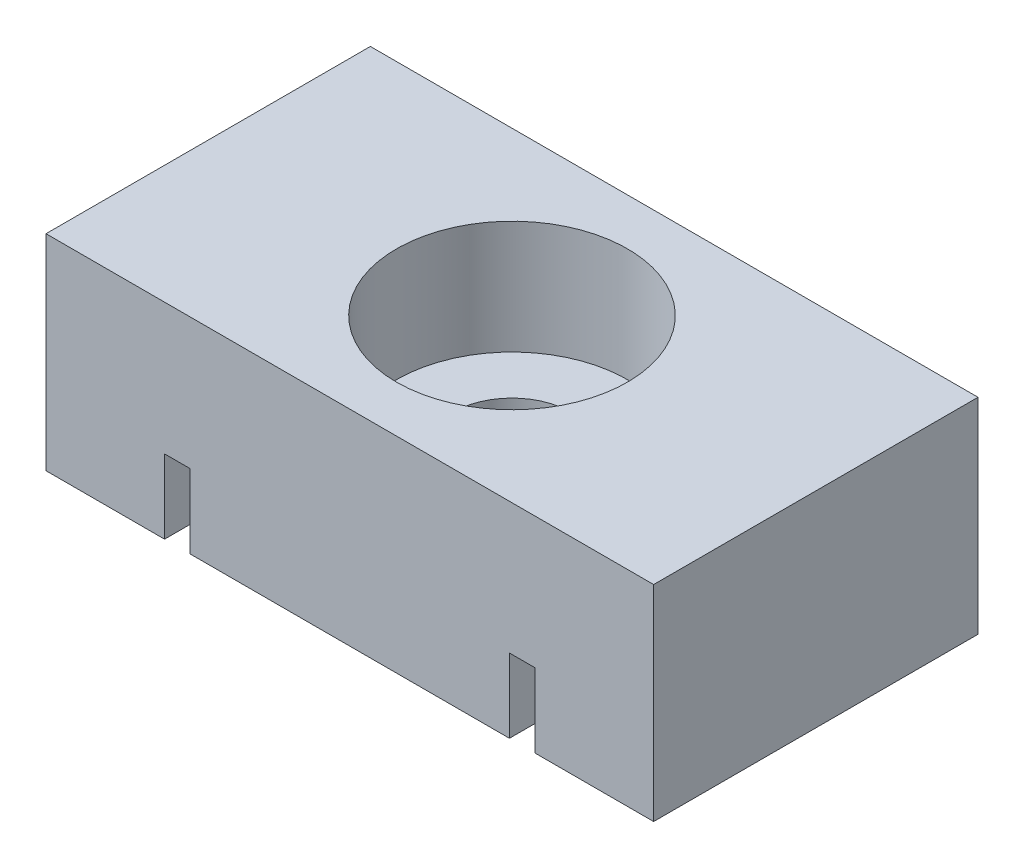
SolidWorks part; units mm, degrees
material "2024 Alloy"
ref_plane "Front Plane" through (0, 0, 0) normal (0, 0, 1) x (1, 0, 0)
ref_plane "Top Plane" through (0, 0, 0) normal (0, 1, 0) x (1, 0, 0)
ref_plane "Right Plane" through (0, 0, 0) normal (1, 0, 0) x (0, 0, -1)
sketch "Sketch1" plane through (0, 0, 0) normal (0, 1, 0) x (1, 0, 0)
  line L1 (-9.398, -5.0165) -> (9.398, -5.0165)
  line L2 (-9.398, -5.0165) -> (-9.398, 5.0165)
  line L3 (-9.398, 5.0165) -> (9.398, 5.0165)
  line L4 (9.398, -5.0165) -> (9.398, 5.0165)
  line L5 (-9.398, -5.0165) -> (9.398, 5.0165) construction
  line L6 (-9.398, 5.0165) -> (9.398, -5.0165) construction
  point P0 (0, 0)
  dimension "D1" = 18.796
  dimension "D2" = 10.033
extrude "Base" add sketch "Sketch1" along normal blind 6.35
sketch "Sketch2" plane through (0, 0, 0) normal (0, -1, 0) x (1, 0, 0)
  line L0 (-5.334, 5.0165) -> (-5.334, 3.5433) construction
  line L1 (-9.398, 5.0165) -> (9.398, 5.0165) construction
  line L2 (-4.9371, 5.0165) -> (-4.9371, 3.5433)
  line L3 (-5.7309, 5.0165) -> (-5.7309, 3.5433)
  line L4 (5.334, 5.0165) -> (5.334, 3.5433) construction
  line L5 (5.7309, 5.0165) -> (5.7309, 3.5433)
  line L6 (4.9371, 5.0165) -> (4.9371, 3.5433)
  line L7 (0, 0) -> (0, 225.9023) construction
  arc A0 (-4.9371, 5.0165) -> (-5.7309, 5.0165) centre (-5.334, 5.0165) ccw
  arc A1 (-5.7309, 3.5433) -> (-4.9371, 3.5433) centre (-5.334, 3.5433) ccw
  arc A2 (5.7309, 5.0165) -> (4.9371, 5.0165) centre (5.334, 5.0165) ccw
  arc A3 (4.9371, 3.5433) -> (5.7309, 3.5433) centre (5.334, 3.5433) ccw
  point P4 (-5.334, 4.2799)
  point P9 (5.334, 4.2799)
  dimension "D1" = 0.7937
  dimension "D2" = 10.668
  dimension "D3" = 1.4732
extrude "BoxSlots" cut sketch "Sketch2" against normal blind 2.286
hole_wizard "MoutingHole" positions "Sketch6" profile "Sketch5" counterbore size "#6" standard "ANSI Inch" end condition through all
sketch "Sketch6" plane through (0, 6.35, 0) normal (0, 1, 0) x (1, 0, 0)
  point P0 (0, 0)
sketch "Sketch5" plane through (0, 6.35, 0) normal (1, 0, 0) x (0, 0, 1)
  line L0 (0, 0) -> (0, 6.35)
  line L1 (0, 6.35) -> (1.8288, 6.35)
  line L3 (1.8288, 6.35) -> (1.8288, 3.5052)
  line L4 (1.8288, 3.5052) -> (3.5725, 3.5052)
  line L5 (3.5725, 3.5052) -> (3.5725, 0)
  line L7 (3.5725, 0) -> (0, 0)
  line L11 (0, -6.35) -> (0, 107.95) construction
  dimension "Thru Hole Dia." = 3.6576
  dimension "Thru Hole Depth" = 6.35
  dimension "C'Bore Dia." = 7.145
  dimension "C'Bore Depth" = 3.5052
